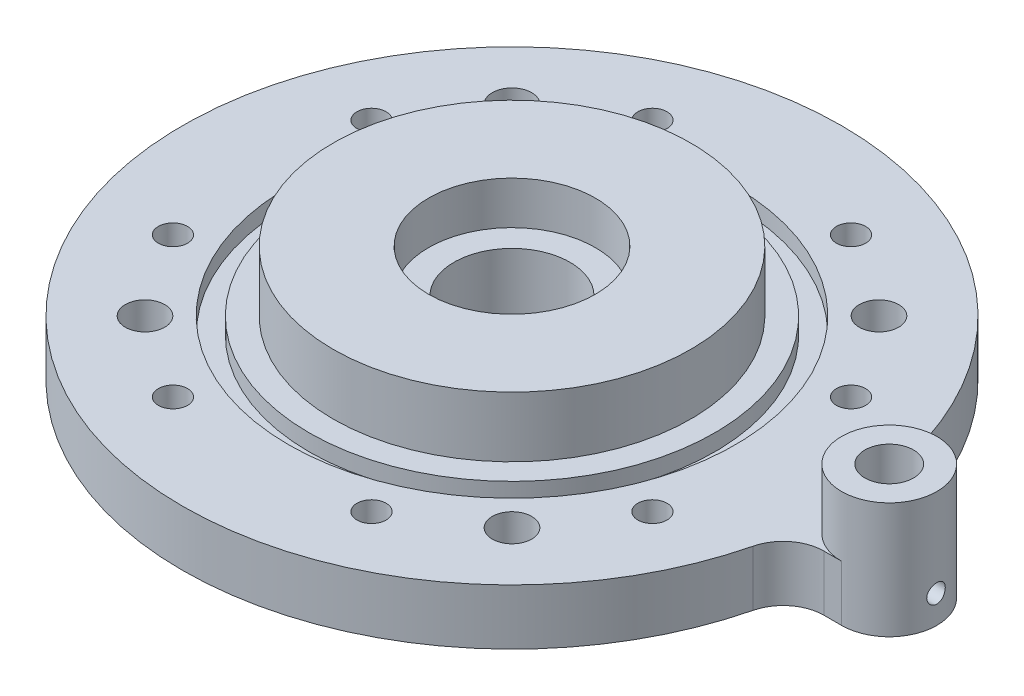
SolidWorks part; units mm, degrees
material "1060 Alloy"
ref_plane "Front" through (0, 0, 0) normal (0, 0, 1) x (1, 0, 0)
ref_plane "Top" through (0, 0, 0) normal (0, 1, 0) x (1, 0, 0)
ref_plane "Right" through (0, 0, 0) normal (1, 0, 0) x (0, 0, -1)
sketch "Sketch1" plane through (0, 0, 0) normal (0, 1, 0) x (1, 0, 0)
  line L0 (56.45, 0) -> (64.6172, 0) construction
  line L1 (61.6105, 8.1672) -> (64.6172, 8.1672)
  line L2 (61.6105, -8.1672) -> (64.6172, -8.1672)
  line L3 (56.45, 0) -> (72.7844, 0) construction
  arc A0 (54.8135, 13.4939) -> (54.8135, -13.4939) centre (0, 0) ccw
  circle A1 centre (0, 0) radius 56.45 construction
  arc A2 (64.6172, -8.1672) -> (64.6172, 8.1672) centre (64.6172, 0) ccw
  arc A3 (54.8135, 13.4939) -> (61.6105, 8.1672) centre (61.6105, 15.1672) ccw
  arc A4 (61.6105, -8.1672) -> (54.8135, -13.4939) centre (61.6105, -15.1672) ccw
  point P5 (34.5422, 0)
  point P10 (55.8561, 8.1672)
  dimension "D1" = 112.9
  dimension "D4" = 7
  dimension "D2" = 16.3344
  dimension "D3" = 16.3344
extrude "base" add sketch "Sketch1" along normal blind 9.525
sketch "Sketch2" plane through (0, 9.525, 0) normal (0, 1, 0) x (1, 0, 0)
  line L0 (64.6172, 8.1672) -> (64.6172, -8.1672) construction
  circle A0 centre (0, 0) radius 30.6267
  arc A1 (64.6172, -8.1672) -> (64.6172, 8.1672) centre (64.6172, 0) ccw construction
  circle A2 centre (64.6172, 0) radius 8.1672
  circle A3 centre (64.6172, 0) radius 4.1672
  dimension "D1" = 61.2534
  dimension "D2" = 8.3344
sketch "Sketch3" plane through (0, 0, 0) normal (0, -1, 0) x (1, 0, 0)
  line L0 (0, 0) -> (72.7844, 0) construction
  line L1 (0, 0) -> (39.9162, -39.9162) construction
  circle A0 centre (0, 0) radius 44.45 construction
  circle A1 centre (-31.4309, -31.4309) radius 3.3734
  circle A2 centre (-31.4309, 31.4309) radius 3.3734
  circle A3 centre (31.4309, 31.4309) radius 3.3734
  circle A4 centre (31.4309, -31.4309) radius 3.3734
  arc A5 (64.6172, -8.1672) -> (64.6172, 8.1672) centre (64.6172, 0) ccw construction
  arc A6 (54.8135, 13.4939) -> (54.8135, -13.4939) centre (0, 0) ccw construction
  point P14 (0, 0)
  dimension "D1" = 88.9
  dimension "D2" = 6.7469
  dimension "D4" = 45
  dimension "D3" = 4
extrude "square bolt holes" cut sketch "Sketch3" against normal through all
sketch "Sketch4" plane through (0, 9.525, 0) normal (0, 1, 0) x (1, 0, 0)
  line L0 (0, 0) -> (0, 44.45) construction
  line L1 (0, 44.45) -> (0, 0) construction
  line L2 (0, 0) -> (17.0103, 41.0664) construction
  circle A0 centre (0, 0) radius 44.45 construction
  circle A1 centre (17.0103, 41.0664) radius 2.5
  dimension "D1" = 88.9
  dimension "D3" = 5
  dimension "D2" = 22.5
extrude "housing bolts" cut sketch "Sketch4" against normal blind 44.33
pattern_circular "CirPattern1" count 8 over 360 about axis through (0, 9.525, 0) along (0, 1, 0) of "housing bolts"
extrude "impeller cavity riser" add sketch "Sketch2" along normal blind 10.3422
sketch "Sketch5" plane through (0, 19.8672, 0) normal (0, 1, 0) x (1, 0, 0)
  circle A0 centre (0, 0) radius 14.2875
  dimension "D1" = 28.575
extrude "seal bore" cut sketch "Sketch5" against normal blind 7.35
sketch "Sketch6" plane through (0, 12.5172, 0) normal (0, 1, 0) x (1, 0, 0)
  circle A0 centre (0, 0) radius 9.9375
  dimension "D1" = 19.875
extrude "bore" cut sketch "Sketch6" against normal blind 39.3
sketch "pressure tap plane alignment" plane through (0, 0, 0) normal (0, -1, 0) x (1, 0, 0)
  line L1 (0, 0) -> (56.45, 0) construction
  line L2 (56.45, 0) -> (56.45, 56.45) construction
  line L3 (56.45, 56.45) -> (0, 56.45) construction
  circle A0 centre (0, 0) radius 56.45 construction
  circle A1 centre (0, 0) radius 56.45 construction
ref_plane "pressure tap plane" through (56.45, 0, 0) normal (1, 0, 0) x (0, 0, -1)
sketch "Sketch9" plane through (56.45, 0, 0) normal (1, 0, 0) x (0, 0, -1)
  line L0 (0, 0) -> (0, 9.525) construction
  line L1 (56.45, 9.525) -> (-56.45, 9.525) construction
  circle A0 centre (0, 4.7625) radius 1.5875
  dimension "D1" = 3.175
extrude "pressure tap" cut sketch "Sketch9" against normal blind 56.45 and the other way through all
sketch "Sketch10" plane through (0, 9.525, 0) normal (0, 1, 0) x (1, 0, 0)
  circle A0 centre (64.6172, 0) radius 1.5875
  dimension "D1" = 3.175
extrude "pressure tap vertical hole" cut sketch "Sketch10" against normal blind 6.35
sketch "Sketch12" plane through (0, 9.525, 0) normal (0, 1, 0) x (1, 0, 0)
  circle A0 centre (0, 0) radius 34.7218
  circle A1 centre (0, 0) radius 38.2524
  dimension "D1" = 76.5048
  dimension "D2" = 69.4436
extrude "Cut-Extrude1" cut sketch "Sketch12" against normal blind 2.8245
equation "\"de\" = 0.426in\t\t\t'entrance eye diameter"
equation "\"d2\" = 2.097in \t\t\t'outer diameter of the impeller"
equation "\"d_exit\" = 0.18in \t\t'volute throat aka D4"
equation "\"theta\" = 25\t\t\t'angle of blades from inner to outer "
equation "\"impeller upper clearance\"= .5mm"
equation "\"impeller horizontal clearance\"= (\"d2\"*1.15 - \"d2\")/2 \t\t'clearance based on D2-D3 ratio for circular volute, ranges 1.15 to 1.2"
equation "\"impeller bottom clearance\"= .5mm"
equation "\"impeller base thickness\"= 2mm"
equation "\"impeller dowel diameter\" = 2mm"
equation "\"impeller bolt head diameter\" = \"m4 head bore diameter\""
equation "\"impeller bolt head depth\" = 4mm"
equation "\"impeller bolt stop depth\" = 3mm"
equation "\"impeller bolt bore\" = \"m4 clearance\""
equation "\"impeller shaft bore depth\" = 12mm"
equation "\"impeller shaft bore\" = 8mm"
equation "\"impeller boss depth\" = \"impeller shaft bore depth\"+\"impeller bolt stop depth\"+\"impeller bolt head depth\"-\"impeller base thickness\""
equation "\"impeller boss diameter\" = \"upper seal ID\""
equation "\"impeller dowel length\" = 2mm*2 + \"impeller shaft bore\""
equation "\"coupler motor shaft hole ID\"= 8mm"
equation "\"coupler OD\"= 17mm"
equation "\"coupler length\"= 25mm"
equation "\"motor OD\" = 64mm"
equation "\"motor shaft diameter\"= 8mm"
equation "\"motor shaft pride\"= 32mm"
equation "\"motor to bearing plate distance\" = \"motor shaft pride\" + 2mm +\"coupler length\"/2"
equation "\"square plate bolt bore\" = 8mm"
equation "\"square plate bolt head diameter\" = 13.5mm"
equation "\"square plate bolt pattern diameter\"= 3.5in"
equation "\"motor mount center bore\"= \"coupler OD\"+ 4mm"
equation "\"motor mount post radius\"= ( 3 * \"square plate bolt bore\" ) / 2"
equation "\"motor mount m4 screw hole diameter\"= 4mm"
equation "\"motor mount m4 head diameter\"= 7.25mm"
equation "\"motor mount m4 head depth\"= 4mm"
equation "\"motor mount m4 pattern diamater\" = 30mm"
equation "\"motor mount plate thickness\"= 8mm + \"motor mount m4 head depth\""
equation "\"shaft coupler section diameter\" = 8mm"
equation "\"shaft coupler section length\" = \"motor to bearing plate distance\" - \"motor shaft pride\" - 2mm"
equation "\"shaft bearing section diameter\" = \"bearing ID\""
equation "\"shaft bearing section length\" = \"bearing plate stop depth\" + \"bearing depth\""
equation "\"shaft bearing stop diameter\" = \"bearing ID\" + 4mm"
equation "\"shaft bearing stop length\" = 3mm"
equation "\"impeller cavity center height\"= \"impeller bottom clearance\" + \"impeller upper clearance\" + \"impeller center height\""
equation "\"impeller cavity diameter\"= 2 * \"impeller horizontal clearance\" + \"d2\" \t\t\t\t\t\t\t\t\t'called D3 analytically"
equation "\"impeller cavity outer height\"= \"impeller bottom clearance\" + \"impeller upper clearance\" + \"impeller base thickness\" + \"b2\" \t\t'this is height at impeller diameter d2, not at d3"
equation "\"impeller housing thickness\"= \"impeller housing exit threaded diameter\" + 2*\"impeller housing outlet grip\""
equation "\"impeller housing diameter\" = \"square plate bolt pattern diameter\" + 2*\"motor mount post radius\""
equation "\"impeller housing bolt count\" = 8"
equation "\"impeller housing bolt diameter\" = \"m6 clearance\""
equation "\"impeller housing bolt pattern diameter\" = 3.5in"
equation "\"impeller housing threaded inlet diameter\" = 0.6875in \t\t'this is the 11/16 drill size for 1/2 npt fitting"
equation "\"impeller housing threaded inlet depth\"= 15mm"
equation "\"impeller housing exit threaded diameter\"= 0.6875in \t\t'this is the 11/16 drill size for 1/2 npt fitting"
equation "\"impeller housing exit threaded depth\"= 18mm"
equation "\"impeller housing diffuser conical angle\"=10"
equation "\"impeller housing diffuser tangent angle\"=5"
equation "\"impeller housing outlet grip\" = 5mm"
equation "\"D1@Sketch1\"=\"impeller housing diameter\""
equation "\"D1@base\" = \"upper seal plate thickness\""
equation "\"D1@Sketch2\"=\"impeller cavity diameter\""
equation "\"D1@Sketch3\"=\"square plate bolt pattern diameter\""
equation "\"D2@Sketch3\"=\"m8 tap\""
equation "\"D1@square bolt holes\" = \"upper seal plate thickness\" - 2mm"
equation "\"D1@Sketch4\"=\"impeller housing bolt pattern diameter\""
equation "\"D2@Sketch4\"=360/\"impeller housing bolt count\"/2"
equation "\"D3@Sketch4\"=\"m6 tap\""
equation "\"D1@CirPattern1\"=\"impeller housing bolt count\""
equation "\"D1@impeller cavity riser\" = \"upper seal plate riser\""
equation "\"D1@Sketch5\" = \"upper seal OD\""
equation "\"D1@seal bore\" = \"upper seal bore\""
equation "\"D1@Sketch6\" = \"upper seal ID\" + 4mm"
equation "\"D1@Sketch9\" = \"upper seal plate pressure hole diameter\""
equation "\"D1@pressure tap\"=\"impeller housing diameter\"/2"
equation "\"de_length\" = 10mm\t\t'entrance eye consistent length"
equation "\"square plate bolt head depth\" = 8mm"
equation "\"shaft impeller section diameter\" = \"impeller shaft bore\""
equation "\"shaft impeller section length\" = \"upper seal plate thickness\" + \"upper seal plate riser\" + \"impeller bottom clearance\" + \"impeller base thickness\" - \"impeller bolt head depth\" - \"impeller bolt stop depth\""
equation "\"impeller housing diffuser final diameter\" = .5in"
equation "\"D2@Sketch1\" = \"upper seal plate pressure tap diameter\" + \"upper seal plate pressure tap grip\" * 2"
equation "\"D3@Sketch1\" = \"upper seal plate pressure tap diameter\" + \"upper seal plate pressure tap grip\" * 2"
equation "\"D2@pressure tap\"=\"big seal plate pressure tap diameter\"/2+\"big seal plate pressure tap grip\""
equation "\"D2@Sketch2\" = \"upper seal plate pressure tap diameter\""
equation "\"D1@Sketch10\" = \"upper seal plate pressure hole diameter\""
equation "\"D1@pressure tap vertical hole\"= \"upper seal plate thickness\" / 2 + \"upper seal plate pressure hole diameter\" / 2"
equation "\"end mill size\" = 0.375in\t'for 3/8 endmill"
equation "\"m6 clearance\" = 0.234375in\t'this is 15/64 bit = 5.95mm, could use 6mm bit, B bit for 6.04mm or 1/4 bit for 6.35mm"
equation "\"m6 tap\" = 5mm\t\t\t'5mm is appropriate, could use 13/64 or #5,6,7"
equation "\"m6 head bore diameter\" = 11mm\t\t"
equation "\"m6 head bore depth\" = 7mm\t'actual is 6mm"
equation "\"m8 clearance\" = 0.3125in\t'this is 5/16in for 7.93mm, could use 8mm, O,P, or 21/64"
equation "\"m8 tap\" = 0.265625in\t\t'this is 17/64 for 6.746875mm"
equation "\"m8 head bore diameter\" = 14mm"
equation "\"m8 head bore depth\" = 9mm\t'actual is 8mm"
equation "\"ce\" = 3.14*\"de\"\t\t'entrance eye circumference"
equation "\"s_open\" = \"av\"/\"b1\"\t\t'width of open area"
equation "\"impeller center height\" = \"impeller base thickness\" + \"b1\"\t'impeller height at de"
equation "\"impeller outer height\" = \"impeller base thickness\" + \"b2\"\t'impeller height at de"
equation "\"lower seal OD\" = .917in\t\t'this is https://www.mcmaster.com/#9281k121/=174001b"
equation "\"lower seal ID\"= .375in"
equation "\"lower seal depth\" = .625in + .218in"
equation "\"lower seal bore\" = \"lower seal depth\" + 1mm"
equation "\"upper seal OD\" = 1.125in\t'this is https://www.mcmaster.com/#5154t33/=173zuau, needs to be visually inspected before machining!"
equation "\"upper seal ID\"= 0.625in"
equation "\"upper seal depth\"= .25in\t'aka height; these values need to be confirmed by inspection!! We may want to compress the height."
equation "\"upper seal bore\" = \"upper seal depth\" + 1mm"
equation "\"lower seal plate lip depth\" = 2mm"
equation "\"lower seal plate lip ID\" = \"lower seal OD\" - 3mm"
equation "\"lower seal plate thickness\" = \"lower seal plate lip depth\" + \"lower seal bore\""
equation "\"shaft lower seal section diameter\" = \"lower seal ID\""
equation "\"shaft lower seal section length\" = \"lower seal plate thickness\" + 1mm"
equation "\"upper seal plate thickness\" = \"upper seal plate pressure hole diameter\"*3"
equation "\"upper seal plate lip ID\" = \"upper seal OD\" - 3mm"
equation "\"upper seal plate riser\" = \"impeller housing thickness\"/2 - \"b2\"/2 - \"impeller base thickness\" - \t\"impeller bottom clearance\"\t\t\t'this offsets the gap under the housing"
equation "\"upper seal plate pressure hole diameter\" = .125in\t'this is 1/8 drill "
equation "\"upper seal plate pressure tap diameter\" = .328125in \t'this is 21/64 drill for a 1/8 ANPT tap"
equation "\"upper seal plate pressure tap grip\" = 4mm\t\t'this is the area around the tap so it doesn't crack"
equation "\"upper seal plate pressure tap depth\" = 12"
equation "\"bearing OD\" = 30mm"
equation "\"bearing ID\"= 10mm"
equation "\"bearing depth\"= 9mm"
equation "\"bearing outer race thickness\"= 1mm"
equation "\"bearing inner race thickness\"= 1mm"
equation "\"bearing bore\" = \"bearing depth\" + 1mm"
equation "\"z\" = 8 \t\t\t'number of blades"
equation "\"b2\" = .07in\t\t\t\t\t\t\t'tip height from disc surface at d2"
equation "\"b1\" = \"b2\" + (\"d2\"/2 - \"de\"/2)*sin(\"theta\") \t\t\t'tip height from disc surface at inlet eye"
equation "\"ae\" = 3.14*(\"de\"^2)/4\t\t'entrance eye area'"
equation "\"av_ratio\" = .325\t\t'ratio of av/ae at N_s of 470, range is .275 to .375, .325 ideal. High ratio means bigger area means smaller blades"
equation "\"av\" = \"ae\"*\"av_ratio\"\t\t'area between just two blades"
equation "\"s\"=\"ce\" - \"z\"*\"s_open\""
equation "\"bearing plate stop ID\" = \"bearing OD\" - 4mm"
equation "\"bearing plate stop depth\" = 3mm"
equation "\"bearing plate thickness\" = \"bearing bore\" + \"bearing plate stop depth\" + \"shaft bearing stop length\""
equation "\"m4 clearance\" = 0.171875in \t'this is 11/64 bit for 4.36mm"
equation "\"m4 tap\" = 0.125in\t\t'this is 1/8 bit for 3.17mm"
equation "\"m4 head bore diameter\" = 7.5mm"
equation "\"m4 head bore depth\" = 5mm\t'actual is ~4mm"
equation "\"big o-ring thickness\" = .139in"
equation "\"big o-ring OD\" = 2.734in"
equation "\"big o-ring ID\" = 3.012in"
equation "\"big o-ring groove depth\" = \"big o-ring thickness\"*4/5"
equation "\"D1@Sketch12\"=\"big o-ring ID\""
equation "\"D2@Sketch12\"=\"big o-ring OD\""
equation "\"D1@Cut-Extrude1\"=\"big o-ring groove depth\""
